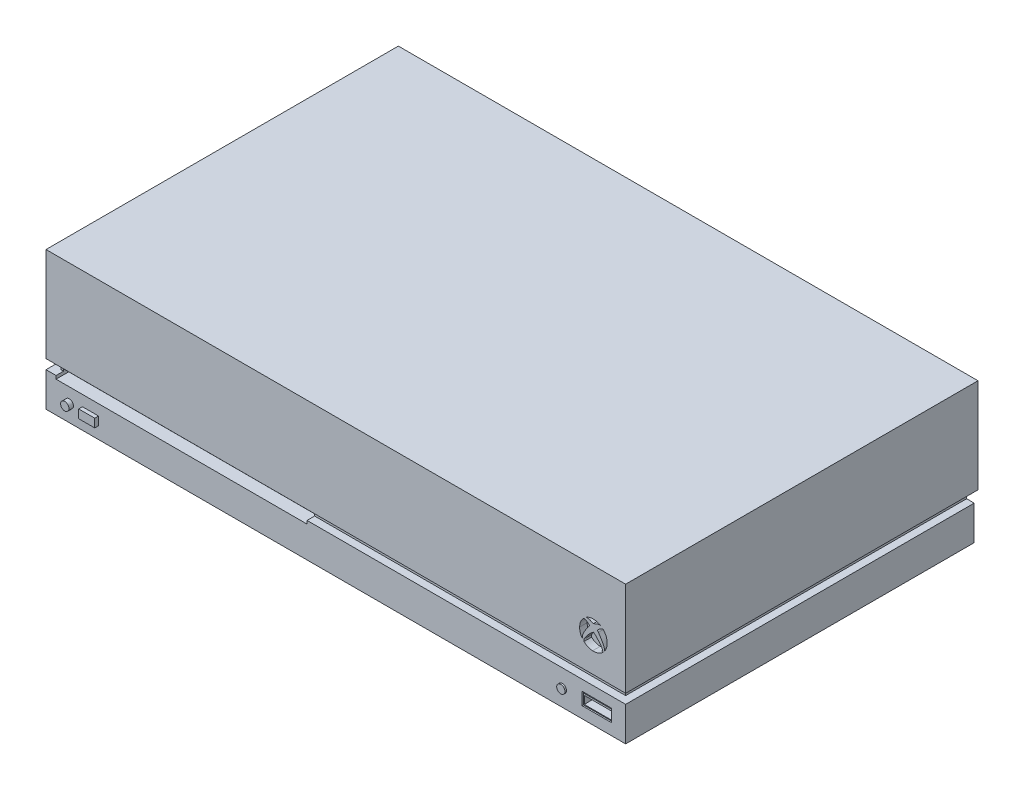
SolidWorks part; units mm, degrees
ref_plane "Front Plane" through (0, 0, 0) normal (0, 0, 1) x (1, 0, 0)
ref_plane "Top Plane" through (0, 0, 0) normal (0, 1, 0) x (1, 0, 0)
ref_plane "Right Plane" through (0, 0, 0) normal (1, 0, 0) x (0, 0, -1)
sketch "Sketch1" plane through (0, 0, 0) normal (0, 1, 0) x (1, 0, 0)
  line L0 (-74.7377, 40.0336) -> (-74.7377, -77.0687)
  line L1 (-74.7377, -77.0687) -> (137.3702, -77.0687)
  line L2 (137.3702, -77.0687) -> (137.3702, 40.0336)
  line L3 (137.3702, 40.0336) -> (-74.7377, 40.0336)
extrude "Boss-Extrude1" add sketch "Sketch1" along normal blind 31.75
sketch "Sketch2" plane through (0, 0, 0) normal (0, -1, 0) x (1, 0, 0)
  line L0 (137.3702, 77.0687) -> (137.3702, -40.0336)
  line L1 (137.3702, -40.0336) -> (-57.3628, -40.0336)
  line L2 (137.3702, -40.0336) -> (-74.7377, -40.0336) construction
  line L3 (-57.3628, -40.0336) -> (-57.3628, 77.0687)
  line L4 (-74.7377, 77.0687) -> (137.3702, 77.0687) construction
  line L5 (-57.3628, 77.0687) -> (137.3702, 77.0687)
extrude "Boss-Extrude2" add sketch "Sketch2" along normal blind 14.732
sketch "Sketch3" plane through (0, 0, 77.0687) normal (0, 0, 1) x (1, 0, 0)
  line L0 (-57.3628, 0) -> (137.3702, 0)
  line L1 (137.3702, 31.75) -> (137.3702, -14.732) construction
  line L2 (137.3702, 0) -> (137.3702, -3.2162)
  line L3 (137.3702, -3.2162) -> (-57.3628, -3.2162)
  line L4 (-57.3628, -14.732) -> (-57.3628, 0) construction
  line L5 (-57.3628, -3.2162) -> (-57.3628, 0)
extrude "Cut-Extrude1" cut sketch "Sketch3" against normal blind 2.54
sketch "Sketch4" plane through (137.3702, 0, 0) normal (1, 0, 0) x (0, 0, -1)
  line L0 (-77.0687, 0) -> (-77.0687, -3.2162)
  line L1 (-77.0687, -3.2162) -> (40.0336, -3.2162)
  line L2 (40.0336, 31.75) -> (40.0336, -14.732) construction
  line L3 (40.0336, -3.2162) -> (40.0336, 0)
  line L4 (40.0336, 0) -> (-77.0687, 0)
extrude "Cut-Extrude2" cut sketch "Sketch4" against normal blind 2.54
sketch "Sketch5" plane through (0, 0, -40.0336) normal (0, 0, -1) x (-1, 0, 0)
  line L0 (-137.3702, 0) -> (-137.3702, -3.2162)
  line L1 (-137.3702, -3.2162) -> (57.3628, -3.2162)
  line L2 (57.3628, -14.732) -> (57.3628, 0) construction
  line L3 (57.3628, -3.2162) -> (57.3628, 0)
  line L4 (57.3628, 0) -> (-137.3702, 0)
extrude "Cut-Extrude4" cut sketch "Sketch5" against normal blind 2.54
sketch "Sketch6" plane through (-57.3628, 0, 0) normal (-1, 0, 0) x (0, 0, 1)
  line L0 (-37.4936, 0) -> (-37.4936, -3.2162)
  line L1 (-37.4936, -3.2162) -> (74.5287, -3.2162)
  line L2 (74.5287, 0) -> (-37.4936, 0)
  line L3 (74.5287, 0) -> (74.5287, -3.2162)
extrude "Cut-Extrude6" cut sketch "Sketch6" against normal blind 2.54
sketch "Sketch7" plane through (0, 0, 77.0687) normal (0, 0, 1) x (1, 0, 0)
  line L0 (137.3702, -3.2162) -> (137.3702, -14.732) construction
  line L1 (122.7433, -10.922) -> (132.5442, -10.922)
  line L2 (122.7433, -10.922) -> (122.7433, -6.7111)
  line L3 (122.7433, -6.7111) -> (132.5442, -6.7111)
  line L4 (132.5442, -10.922) -> (132.5442, -6.7111)
  line L5 (137.3702, -14.732) -> (-57.3628, -14.732) construction
  dimension "D1" = 3.81
  dimension "D2" = 4.826
extrude "Cut-Extrude8" cut sketch "Sketch7" against normal blind 5.08
sketch "Sketch8" plane through (0, 0, 71.9887) normal (0, 0, 1) x (1, 0, 0)
  line L0 (132.5442, -6.7111) -> (122.7433, -6.7111)
  line L1 (122.7433, -6.7111) -> (122.7433, -10.922)
  line L2 (122.7433, -10.922) -> (132.5442, -10.922)
  line L3 (122.7433, -10.922) -> (132.5442, -10.922) construction
  line L4 (132.5442, -10.922) -> (132.5442, -6.7111) construction
  line L5 (132.5442, -10.922) -> (132.5442, -6.7111)
extrude "Boss-Extrude3" add sketch "Sketch8" along normal blind 4.6314
sketch "Sketch9" plane through (0, 0, 76.6201) normal (0, 0, 1) x (1, 0, 0)
  line L0 (132.4085, -7.994) -> (123.0238, -7.994)
  line L1 (123.0238, -7.994) -> (123.0238, -10.6263)
  line L2 (123.0238, -10.6263) -> (132.4085, -10.6263)
  line L3 (132.4085, -10.6263) -> (132.4085, -7.994)
extrude "Cut-Extrude9" cut sketch "Sketch9" against normal blind 4.6314
sketch "Sketch10" plane through (0, 0, 76.6201) normal (0, 0, 1) x (1, 0, 0)
  line L0 (132.5442, -7.4299) -> (122.7433, -7.4299)
  line L1 (132.5442, -10.922) -> (132.5442, -6.7111) construction
  line L2 (122.7433, -6.7111) -> (122.7433, -10.922) construction
  line L3 (122.7433, -7.4299) -> (122.7433, -6.7111)
  line L4 (132.5442, -6.7111) -> (122.7433, -6.7111) construction
  line L5 (122.7433, -6.7111) -> (132.5442, -6.7111)
  line L6 (132.5442, -6.7111) -> (132.5442, -7.4299)
extrude "Cut-Extrude10" cut sketch "Sketch10" against normal blind 4.6314
sketch "Sketch11" plane through (0, 0, 77.0687) normal (0, 0, 1) x (1, 0, 0)
  circle A0 centre (116.1002, -9.1661) radius 1.397
  dimension "D1" = 2.794
extrude "Boss-Extrude4" add sketch "Sketch11" along normal blind 0.508
sketch "Sketch13" plane through (0, 0, 77.0687) normal (0, 0, 1) x (1, 0, 0)
  circle A0 centre (-49.5395, -9.1661) radius 1.397
  dimension "D1" = 2.794
extrude "Boss-Extrude5" add sketch "Sketch13" along normal blind 1.524
sketch "Sketch14" plane through (0, 0, 77.0687) normal (0, 0, 1) x (1, 0, 0)
  line L0 (-53.9904, -3.2162) -> (-53.9904, -4.2897)
  line L1 (-57.3628, -3.2162) -> (137.3702, -3.2162) construction
  line L2 (-53.9904, -4.2897) -> (30.3322, -4.2897)
  line L3 (30.3322, -4.2897) -> (30.3322, -3.2162)
  line L4 (30.3322, -3.2162) -> (-53.9904, -3.2162)
extrude "Cut-Extrude12" cut sketch "Sketch14" against normal blind 12.7
sketch "Sketch15" plane through (0, 0, 74.5287) normal (0, 0, 1) x (1, 0, 0)
  line L0 (-53.9904, -3.2162) -> (-53.9904, -2.9114)
  line L1 (-53.9904, -2.9114) -> (30.3322, -2.9114)
  line L2 (30.3322, -2.9114) -> (30.3322, -3.2162)
  line L3 (30.3322, -3.2162) -> (-53.9904, -3.2162)
  dimension "D1" = 0.3048
extrude "Cut-Extrude14" cut sketch "Sketch15" against normal blind 10.16
sketch "Sketch17" plane through (0, 0, 77.0687) normal (0, 0, 1) x (1, 0, 0)
  line L0 (-39.7277, -7.8666) -> (-45.1141, -7.8666)
  line L1 (-45.1141, -7.8666) -> (-45.1141, -10.7177)
  line L2 (-45.1141, -10.7177) -> (-39.7277, -10.7177)
  line L3 (-39.7277, -10.7177) -> (-39.7277, -7.8666)
extrude "Boss-Extrude7" add sketch "Sketch17" along normal blind 1.27
sketch "Sketch19" plane through (0, 0, 77.0687) normal (0, 0, 1) x (1, 0, 0)
  line L0 (-65.632, 31.75) -> (-65.632, 0)
  line L1 (-74.7377, 31.75) -> (137.3702, 31.75) construction
  line L2 (-74.7377, 0) -> (137.3702, 0) construction
  line L3 (-65.632, 0) -> (-74.7377, 0)
  line L4 (-74.7377, 0) -> (-74.7377, 31.75)
  line L5 (-74.7377, 31.75) -> (-65.632, 31.75)
extrude "Cut-Extrude17" cut sketch "Sketch19" against normal blind 133.35
sketch "Sketch20" plane through (0, 0, 74.5287) normal (0, 0, 1) x (1, 0, 0)
  line L0 (30.3322, -2.9114) -> (30.3322, -2.5679)
  line L1 (30.3322, -2.5679) -> (-53.9904, -2.5679)
  line L2 (-53.9904, -2.5679) -> (-53.9904, -2.9114)
  line L3 (-53.9904, -2.9114) -> (30.3322, -2.9114)
extrude "Cut-Extrude20" cut sketch "Sketch20" against normal blind 10.16
sketch "Sketch21" plane through (0, 0, -37.4936) normal (0, 0, -1) x (-1, 0, 0)
  line L0 (-134.8302, 0) -> (-134.8302, -3.2162)
  line L1 (-134.8302, -3.2162) -> (54.8228, -3.2162)
  line L2 (54.8228, -3.2162) -> (54.8228, 0)
  line L3 (54.8228, 0) -> (-134.8302, 0)
extrude "Boss-Extrude8" add sketch "Sketch21" along normal blind 2.54
sketch "Sketch24" plane through (0, 0, -40.0336) normal (0, 0, -1) x (-1, 0, 0)
  line L0 (-135.3382, 29.718) -> (63.6, 29.718)
  line L1 (63.6, 29.718) -> (63.6, 0)
  line L2 (-135.3382, 29.718) -> (-135.3382, 0)
  line L3 (-137.3702, 0) -> (-134.8302, 0) construction
  line L5 (54.8228, 0) -> (65.632, 0) construction
  line L6 (-137.3702, 31.75) -> (-137.3702, 0) construction
  line L7 (65.632, 0) -> (65.632, 31.75) construction
  line L8 (-137.3702, 31.75) -> (65.632, 31.75) construction
  line L21 (57.3628, -14.732) -> (57.3628, -3.2162)
  line L22 (57.3628, -3.2162) -> (54.8228, -3.2162)
  line L23 (54.8228, -3.2162) -> (54.8228, 0)
  line L24 (54.8228, 0) -> (65.632, 0)
  line L25 (65.632, 0) -> (65.632, 31.75)
  line L26 (65.632, 31.75) -> (-137.3702, 31.75)
  line L27 (-137.3702, 31.75) -> (-137.3702, 0)
  line L28 (-137.3702, 0) -> (-134.8302, 0)
  line L29 (-134.8302, 0) -> (-134.8302, -3.2162)
  line L30 (-134.8302, -3.2162) -> (-137.3702, -3.2162)
  line L31 (-137.3702, -3.2162) -> (-137.3702, -14.732)
  line L32 (-137.3702, -14.732) -> (57.3628, -14.732)
  line L36 (63.6, 0) -> (65.632, 0)
  line L37 (65.632, 0) -> (65.632, 31.75)
  line L38 (65.632, 31.75) -> (-137.3702, 31.75)
  line L39 (-137.3702, 31.75) -> (-137.3702, 0)
  line L40 (-137.3702, 0) -> (-135.3382, 0)
  dimension "D1" = 2.032
  dimension "D2" = 2.032
  dimension "D3" = 2.032
  dimension "D4" = 0
extrude "Boss-Extrude9" add sketch "Sketch24" along normal blind 1.27 contours L36 L37 L38 L39 L40 L2 L0 L1
sketch "Sketch25" plane through (0, 0, -40.0336) normal (0, 0, -1) x (-1, 0, 0)
  circle A0 centre (-131.916, 26.6592) radius 0.9515
  circle A1 centre (-129.376, 26.6592) radius 0.9515
  circle A2 centre (-126.836, 26.6592) radius 0.9515
  circle A3 centre (-124.296, 26.6592) radius 0.9515
  circle A4 centre (-121.756, 26.6592) radius 0.9515
  circle A5 centre (-119.216, 26.6592) radius 0.9515
  circle A6 centre (-116.676, 26.6592) radius 0.9515
  circle A7 centre (-114.136, 26.6592) radius 0.9515
  circle A8 centre (-111.596, 26.6592) radius 0.9515
  circle A9 centre (-109.056, 26.6592) radius 0.9515
  circle A10 centre (-106.516, 26.6592) radius 0.9515
  circle A11 centre (-103.976, 26.6592) radius 0.9515
  circle A12 centre (-101.436, 26.6592) radius 0.9515
  circle A13 centre (-98.896, 26.6592) radius 0.9515
  circle A14 centre (-96.356, 26.6592) radius 0.9515
  circle A15 centre (-93.816, 26.6592) radius 0.9515
  circle A16 centre (-91.276, 26.6592) radius 0.9515
  circle A17 centre (-88.736, 26.6592) radius 0.9515
  circle A18 centre (-86.196, 26.6592) radius 0.9515
  circle A19 centre (-83.656, 26.6592) radius 0.9515
  circle A20 centre (-81.116, 26.6592) radius 0.9515
  circle A21 centre (-78.576, 26.6592) radius 0.9515
  circle A22 centre (-76.036, 26.6592) radius 0.9515
  circle A23 centre (-73.496, 26.6592) radius 0.9515
  circle A24 centre (-70.956, 26.6592) radius 0.9515
  circle A25 centre (-68.416, 26.6592) radius 0.9515
  circle A26 centre (-65.876, 26.6592) radius 0.9515
  circle A27 centre (-63.336, 26.6592) radius 0.9515
  circle A28 centre (-60.796, 26.6592) radius 0.9515
  circle A29 centre (-58.256, 26.6592) radius 0.9515
  circle A30 centre (-55.716, 26.6592) radius 0.9515
  circle A31 centre (-53.176, 26.6592) radius 0.9515
  circle A32 centre (-50.636, 26.6592) radius 0.9515
  circle A33 centre (-48.096, 26.6592) radius 0.9515
  circle A34 centre (-45.556, 26.6592) radius 0.9515
  circle A35 centre (-43.016, 26.6592) radius 0.9515
  circle A36 centre (-40.476, 26.6592) radius 0.9515
  circle A37 centre (-37.936, 26.6592) radius 0.9515
  circle A38 centre (-35.396, 26.6592) radius 0.9515
  circle A39 centre (-32.856, 26.6592) radius 0.9515
  circle A40 centre (-30.316, 26.6592) radius 0.9515
  circle A41 centre (-27.776, 26.6592) radius 0.9515
  circle A42 centre (-25.236, 26.6592) radius 0.9515
  circle A43 centre (-22.696, 26.6592) radius 0.9515
  circle A44 centre (-20.156, 26.6592) radius 0.9515
  circle A45 centre (-17.616, 26.6592) radius 0.9515
  circle A46 centre (-15.076, 26.6592) radius 0.9515
  circle A47 centre (-12.536, 26.6592) radius 0.9515
  circle A48 centre (-9.996, 26.6592) radius 0.9515
  circle A49 centre (-7.456, 26.6592) radius 0.9515
  circle A50 centre (-4.916, 26.6592) radius 0.9515
  circle A51 centre (-2.376, 26.6592) radius 0.9515
  circle A52 centre (0.164, 26.6592) radius 0.9515
  circle A53 centre (2.704, 26.6592) radius 0.9515
  circle A54 centre (5.244, 26.6592) radius 0.9515
  circle A55 centre (7.784, 26.6592) radius 0.9515
  circle A56 centre (10.324, 26.6592) radius 0.9515
  circle A57 centre (12.864, 26.6592) radius 0.9515
  circle A58 centre (15.404, 26.6592) radius 0.9515
  circle A59 centre (17.944, 26.6592) radius 0.9515
  circle A60 centre (20.484, 26.6592) radius 0.9515
  circle A61 centre (23.024, 26.6592) radius 0.9515
  circle A62 centre (25.564, 26.6592) radius 0.9515
  circle A63 centre (-131.916, 24.1192) radius 0.889
  circle A64 centre (-129.376, 24.1192) radius 0.889
  circle A65 centre (-126.836, 24.1192) radius 0.889
  circle A66 centre (-124.296, 24.1192) radius 0.889
  circle A67 centre (-121.756, 24.1192) radius 0.889
  circle A68 centre (-119.216, 24.1192) radius 0.889
  circle A69 centre (-116.676, 24.1192) radius 0.889
  circle A70 centre (-114.136, 24.1192) radius 0.889
  circle A71 centre (-111.596, 24.1192) radius 0.889
  circle A72 centre (-109.056, 24.1192) radius 0.889
  circle A73 centre (-106.516, 24.1192) radius 0.889
  circle A74 centre (-103.976, 24.1192) radius 0.889
  circle A75 centre (-101.436, 24.1192) radius 0.889
  circle A76 centre (-98.896, 24.1192) radius 0.889
  circle A77 centre (-96.356, 24.1192) radius 0.889
  circle A78 centre (-93.816, 24.1192) radius 0.889
  circle A79 centre (-91.276, 24.1192) radius 0.889
  circle A80 centre (-88.736, 24.1192) radius 0.889
  circle A81 centre (-86.196, 24.1192) radius 0.889
  circle A82 centre (-83.656, 24.1192) radius 0.889
  circle A83 centre (-81.116, 24.1192) radius 0.889
  circle A84 centre (-78.576, 24.1192) radius 0.889
  circle A85 centre (-76.036, 24.1192) radius 0.889
  circle A86 centre (-73.496, 24.1192) radius 0.889
  circle A87 centre (-70.956, 24.1192) radius 0.889
  circle A88 centre (-68.416, 24.1192) radius 0.889
  circle A89 centre (-65.876, 24.1192) radius 0.889
  circle A90 centre (-63.336, 24.1192) radius 0.889
  circle A91 centre (-60.796, 24.1192) radius 0.889
  circle A92 centre (-58.256, 24.1192) radius 0.889
  circle A93 centre (-55.716, 24.1192) radius 0.889
  circle A94 centre (-53.176, 24.1192) radius 0.889
  circle A95 centre (-50.636, 24.1192) radius 0.889
  circle A96 centre (-48.096, 24.1192) radius 0.889
  circle A97 centre (-45.556, 24.1192) radius 0.889
  circle A98 centre (-43.016, 24.1192) radius 0.889
  circle A99 centre (-40.476, 24.1192) radius 0.889
  circle A100 centre (-37.936, 24.1192) radius 0.889
  circle A101 centre (-35.396, 24.1192) radius 0.889
  circle A102 centre (-32.856, 24.1192) radius 0.889
  circle A103 centre (-30.316, 24.1192) radius 0.889
  circle A104 centre (-27.776, 24.1192) radius 0.889
  circle A105 centre (-25.236, 24.1192) radius 0.889
  circle A106 centre (-22.696, 24.1192) radius 0.889
  circle A107 centre (-20.156, 24.1192) radius 0.889
  circle A108 centre (-17.616, 24.1192) radius 0.889
  circle A109 centre (-15.076, 24.1192) radius 0.889
  circle A110 centre (-12.536, 24.1192) radius 0.889
  circle A111 centre (-9.996, 24.1192) radius 0.889
  circle A112 centre (-7.456, 24.1192) radius 0.889
  circle A113 centre (-4.916, 24.1192) radius 0.889
  circle A114 centre (-2.376, 24.1192) radius 0.889
  circle A115 centre (0.164, 24.1192) radius 0.889
  circle A116 centre (2.704, 24.1192) radius 0.889
  circle A117 centre (5.244, 24.1192) radius 0.889
  circle A118 centre (7.784, 24.1192) radius 0.889
  circle A119 centre (10.324, 24.1192) radius 0.889
  circle A120 centre (12.864, 24.1192) radius 0.889
  circle A121 centre (15.404, 24.1192) radius 0.889
  circle A122 centre (17.944, 24.1192) radius 0.889
  circle A123 centre (20.484, 24.1192) radius 0.889
  circle A124 centre (23.024, 24.1192) radius 0.889
  circle A125 centre (25.564, 24.1192) radius 0.889
  circle A126 centre (-131.916, 21.5792) radius 0.889
  circle A127 centre (-129.376, 21.5792) radius 0.889
  circle A128 centre (-126.836, 21.5792) radius 0.889
  circle A129 centre (-124.296, 21.5792) radius 0.889
  circle A130 centre (-121.756, 21.5792) radius 0.889
  circle A131 centre (-119.216, 21.5792) radius 0.889
  circle A132 centre (-116.676, 21.5792) radius 0.889
  circle A133 centre (-114.136, 21.5792) radius 0.889
  circle A134 centre (-111.596, 21.5792) radius 0.889
  circle A135 centre (-109.056, 21.5792) radius 0.889
  circle A136 centre (-106.516, 21.5792) radius 0.889
  circle A137 centre (-103.976, 21.5792) radius 0.889
  circle A138 centre (-101.436, 21.5792) radius 0.889
  circle A139 centre (-98.896, 21.5792) radius 0.889
  circle A140 centre (-96.356, 21.5792) radius 0.889
  circle A141 centre (-93.816, 21.5792) radius 0.889
  circle A142 centre (-91.276, 21.5792) radius 0.889
  circle A143 centre (-88.736, 21.5792) radius 0.889
  circle A144 centre (-86.196, 21.5792) radius 0.889
  circle A145 centre (-83.656, 21.5792) radius 0.889
  circle A146 centre (-81.116, 21.5792) radius 0.889
  circle A147 centre (-78.576, 21.5792) radius 0.889
  circle A148 centre (-76.036, 21.5792) radius 0.889
  circle A149 centre (-73.496, 21.5792) radius 0.889
  circle A150 centre (-70.956, 21.5792) radius 0.889
  circle A151 centre (-68.416, 21.5792) radius 0.889
  circle A152 centre (-65.876, 21.5792) radius 0.889
  circle A153 centre (-63.336, 21.5792) radius 0.889
  circle A154 centre (-60.796, 21.5792) radius 0.889
  circle A155 centre (-58.256, 21.5792) radius 0.889
  circle A156 centre (-55.716, 21.5792) radius 0.889
  circle A157 centre (-53.176, 21.5792) radius 0.889
  circle A158 centre (-50.636, 21.5792) radius 0.889
  circle A159 centre (-48.096, 21.5792) radius 0.889
  circle A160 centre (-45.556, 21.5792) radius 0.889
  circle A161 centre (-43.016, 21.5792) radius 0.889
  circle A162 centre (-40.476, 21.5792) radius 0.889
  circle A163 centre (-37.936, 21.5792) radius 0.889
  circle A164 centre (-35.396, 21.5792) radius 0.889
  circle A165 centre (-32.856, 21.5792) radius 0.889
  circle A166 centre (-30.316, 21.5792) radius 0.889
  circle A167 centre (-27.776, 21.5792) radius 0.889
  circle A168 centre (-25.236, 21.5792) radius 0.889
  circle A169 centre (-22.696, 21.5792) radius 0.889
  circle A170 centre (-20.156, 21.5792) radius 0.889
  circle A171 centre (-17.616, 21.5792) radius 0.889
  circle A172 centre (-15.076, 21.5792) radius 0.889
  circle A173 centre (-12.536, 21.5792) radius 0.889
  circle A174 centre (-9.996, 21.5792) radius 0.889
  circle A175 centre (-7.456, 21.5792) radius 0.889
  circle A176 centre (-4.916, 21.5792) radius 0.889
  circle A177 centre (-2.376, 21.5792) radius 0.889
  circle A178 centre (0.164, 21.5792) radius 0.889
  circle A179 centre (2.704, 21.5792) radius 0.889
  circle A180 centre (5.244, 21.5792) radius 0.889
  circle A181 centre (7.784, 21.5792) radius 0.889
  circle A182 centre (10.324, 21.5792) radius 0.889
  circle A183 centre (12.864, 21.5792) radius 0.889
  circle A184 centre (15.404, 21.5792) radius 0.889
  circle A185 centre (17.944, 21.5792) radius 0.889
  circle A186 centre (20.484, 21.5792) radius 0.889
  circle A187 centre (23.024, 21.5792) radius 0.889
  circle A188 centre (25.564, 21.5792) radius 0.889
  circle A189 centre (-131.916, 19.0392) radius 0.889
  circle A190 centre (-129.376, 19.0392) radius 0.889
  circle A191 centre (-126.836, 19.0392) radius 0.889
  circle A192 centre (-124.296, 19.0392) radius 0.889
  circle A193 centre (-121.756, 19.0392) radius 0.889
  circle A194 centre (-119.216, 19.0392) radius 0.889
  circle A195 centre (-116.676, 19.0392) radius 0.889
  circle A196 centre (-114.136, 19.0392) radius 0.889
  circle A197 centre (-111.596, 19.0392) radius 0.889
  circle A198 centre (-109.056, 19.0392) radius 0.889
  circle A199 centre (-106.516, 19.0392) radius 0.889
  circle A200 centre (-103.976, 19.0392) radius 0.889
  circle A201 centre (-101.436, 19.0392) radius 0.889
  circle A202 centre (-98.896, 19.0392) radius 0.889
  circle A203 centre (-96.356, 19.0392) radius 0.889
  circle A204 centre (-93.816, 19.0392) radius 0.889
  circle A205 centre (-91.276, 19.0392) radius 0.889
  circle A206 centre (-88.736, 19.0392) radius 0.889
  circle A207 centre (-86.196, 19.0392) radius 0.889
  circle A208 centre (-83.656, 19.0392) radius 0.889
  circle A209 centre (-81.116, 19.0392) radius 0.889
  circle A210 centre (-78.576, 19.0392) radius 0.889
  circle A211 centre (-76.036, 19.0392) radius 0.889
  circle A212 centre (-73.496, 19.0392) radius 0.889
  circle A213 centre (-70.956, 19.0392) radius 0.889
  circle A214 centre (-68.416, 19.0392) radius 0.889
  circle A215 centre (-65.876, 19.0392) radius 0.889
  circle A216 centre (-63.336, 19.0392) radius 0.889
  circle A217 centre (-60.796, 19.0392) radius 0.889
  circle A218 centre (-58.256, 19.0392) radius 0.889
  circle A219 centre (-55.716, 19.0392) radius 0.889
  circle A220 centre (-53.176, 19.0392) radius 0.889
  circle A221 centre (-50.636, 19.0392) radius 0.889
  circle A222 centre (-48.096, 19.0392) radius 0.889
  circle A223 centre (-45.556, 19.0392) radius 0.889
  circle A224 centre (-43.016, 19.0392) radius 0.889
  circle A225 centre (-40.476, 19.0392) radius 0.889
  circle A226 centre (-37.936, 19.0392) radius 0.889
  circle A227 centre (-35.396, 19.0392) radius 0.889
  circle A228 centre (-32.856, 19.0392) radius 0.889
  circle A229 centre (-30.316, 19.0392) radius 0.889
  circle A230 centre (-27.776, 19.0392) radius 0.889
  circle A231 centre (-25.236, 19.0392) radius 0.889
  circle A232 centre (-22.696, 19.0392) radius 0.889
  circle A233 centre (-20.156, 19.0392) radius 0.889
  circle A234 centre (-17.616, 19.0392) radius 0.889
  circle A235 centre (-15.076, 19.0392) radius 0.889
  circle A236 centre (-12.536, 19.0392) radius 0.889
  circle A237 centre (-9.996, 19.0392) radius 0.889
  circle A238 centre (-7.456, 19.0392) radius 0.889
  circle A239 centre (-4.916, 19.0392) radius 0.889
  circle A240 centre (-2.376, 19.0392) radius 0.889
  circle A241 centre (0.164, 19.0392) radius 0.889
  circle A242 centre (2.704, 19.0392) radius 0.889
  circle A243 centre (5.244, 19.0392) radius 0.889
  circle A244 centre (7.784, 19.0392) radius 0.889
  circle A245 centre (10.324, 19.0392) radius 0.889
  circle A246 centre (12.864, 19.0392) radius 0.889
  circle A247 centre (15.404, 19.0392) radius 0.889
  circle A248 centre (17.944, 19.0392) radius 0.889
  circle A249 centre (20.484, 19.0392) radius 0.889
  circle A250 centre (23.024, 19.0392) radius 0.889
  circle A251 centre (25.564, 19.0392) radius 0.889
  dimension "D2" = 2.54
  dimension "D3" = 1.778
  dimension "D4" = 1.9029
  dimension "D6" = 2.54
  dimension "D7" = 1.778
  dimension "D9" = 2.54
  dimension "D10" = 1.778
  dimension "D1" = 63
  dimension "D5" = 63
  dimension "D8" = 63
  dimension "D11" = 63
extrude "Cut-Extrude23" cut sketch "Sketch25" against normal blind 13.97
sketch "Sketch26" plane through (0, 0, -40.0336) normal (0, 0, -1) x (-1, 0, 0)
  line L8 (28.9927, 29.718) -> (28.9927, 0)
  line L9 (-135.3382, 29.718) -> (63.6, 29.718) construction
  line L10 (28.9927, 0) -> (54.8228, 0)
  line L11 (54.8228, 0) -> (54.8228, -0.4442)
  line L12 (54.8228, -3.2162) -> (54.8228, 0) construction
  line L13 (54.8228, -0.4442) -> (28.4648, -0.4442)
  line L14 (28.4648, -0.4442) -> (28.4648, 29.718)
  line L15 (28.4648, 29.718) -> (28.9927, 29.718)
extrude "Cut-Extrude28" cut sketch "Sketch26" against normal blind 13.97 contours L15 L8 L10 L11 L13 L14
sketch "Sketch27" plane through (0, 0, -40.0336) normal (0, 0, -1) x (-1, 0, 0)
  line L5 (43.5719, 14.4052) -> (50.9349, 14.4052)
  line L6 (43.5719, 14.4052) -> (43.5719, 10.9849)
  line L7 (43.5719, 10.9849) -> (50.9349, 10.9849)
  line L8 (50.9349, 14.4052) -> (50.9349, 10.9849)
extrude "Cut-Extrude29" cut sketch "Sketch27" against normal blind 13.97
sketch "Sketch28" plane through (0, 0, -40.0336) normal (0, 0, -1) x (-1, 0, 0)
  line L0 (-126.6517, 5.0454) -> (-120.35, 5.0454) construction
  line L1 (-126.6517, 8.3464) -> (-120.35, 8.3464)
  line L2 (-126.6517, 1.7445) -> (-120.35, 1.7445)
  line L3 (-1000.1763, -459.4468) -> (-111.5096, -459.4468) construction
  line L4 (-83.9499, 4.5855) -> (-86.7908, 1.7445)
  line L5 (-86.7908, 1.7445) -> (-94.3599, 1.7445)
  line L6 (-94.3599, 1.7445) -> (-96.4957, 3.8803)
  line L7 (-96.4957, 3.8803) -> (-96.4957, 7.8543)
  line L8 (-96.4957, 7.8543) -> (-83.9499, 7.8543)
  line L9 (-83.9499, 7.8543) -> (-83.9499, 4.5855)
  line L10 (-65.3081, 7.8543) -> (-65.3081, 4.5855)
  line L11 (-65.3081, 4.5855) -> (-68.149, 1.7445)
  line L12 (-68.149, 1.7445) -> (-75.7181, 1.7445)
  line L13 (-75.7181, 1.7445) -> (-77.8539, 3.8803)
  line L14 (-77.8539, 3.8803) -> (-77.8539, 7.8543)
  line L15 (-77.8539, 7.8543) -> (-65.3081, 7.8543)
  line L16 (-40.9735, 1.7445) -> (-40.9735, 7.8543)
  line L17 (-59.2121, 1.7445) -> (-47.0695, 1.7445)
  line L18 (-59.2121, 1.7445) -> (-59.2121, 7.8543)
  line L19 (-59.2121, 7.8543) -> (-47.0695, 7.8543)
  line L20 (-47.0695, 1.7445) -> (-47.0695, 7.8543)
  line L21 (-40.9735, 1.7445) -> (-28.831, 1.7445)
  line L22 (-28.831, 1.7445) -> (-28.831, 7.8543)
  line L23 (-40.9735, 7.8543) -> (-28.831, 7.8543)
  line L24 (-5.3824, 10.5267) -> (2.9257, 10.5267)
  line L25 (2.9257, 10.5267) -> (2.9257, 0)
  line L26 (2.9257, 0) -> (-5.3824, 0)
  line L27 (-5.3824, 0) -> (-5.3824, 10.5267)
  line L28 (25.0805, 10.5267) -> (15.0682, 10.5267)
  line L29 (15.0682, 10.5267) -> (15.0682, 0)
  line L30 (15.0682, 0) -> (25.0805, 0)
  line L31 (25.0805, 0) -> (25.0805, 10.5267)
  arc A0 (-126.6517, 8.3464) -> (-126.6517, 1.7445) centre (-126.6517, 5.0454) ccw
  arc A1 (-120.35, 1.7445) -> (-120.35, 8.3464) centre (-120.35, 5.0454) ccw
  circle A2 centre (-18.59, 4.5855) radius 2.5563
  circle A3 centre (-18.59, 4.5855) radius 3.8988
  point P2 (-123.5009, 5.0454)
  dimension "D3" = 6.096
  dimension "D4" = 6.096
  dimension "D5" = 6.096
  dimension "D1" = 2
  dimension "D2" = 2
extrude "Cut-Extrude30" cut sketch "Sketch28" against normal blind 7.62
sketch "Sketch29" plane through (0, 0, -40.0336) normal (0, 0, -1) x (-1, 0, 0)
  line L0 (-77.216, 14.2428) -> (-65.4628, 14.2428)
  text T0 "H D M I OUT " font "Century Gothic" height in points 3
sketch "Sketch30" plane through (0, 0, -40.0336) normal (0, 0, -1) x (-1, 0, 0)
  line L0 (-126.6517, 5.0454) -> (-120.35, 5.0454) construction
  line L1 (-126.6517, 6.9588) -> (-120.35, 6.9588)
  line L2 (-126.6517, 3.1321) -> (-120.35, 3.1321)
  arc A1 (-126.6517, 6.9588) -> (-126.6517, 3.1321) centre (-126.6517, 5.0454) ccw
  arc A2 (-120.35, 3.1321) -> (-120.35, 6.9588) centre (-120.35, 5.0454) ccw
  circle A3 centre (-126.6517, 5.0454) radius 1.0146
  circle A4 centre (-120.35, 5.0454) radius 1.1066
  text T0 "H D M I IN" font "Century Gothic" height in points 3
  point P3 (-123.5009, 5.0454)
extrude "Boss-Extrude10" add sketch "Sketch30" against normal blind 3.81
sketch "Sketch31" plane through (0, 0, 77.0687) normal (0, 0, 1) x (1, 0, 0)
  line L0 (292.423, 518.7459) -> (975.0897, 518.7459) construction
  spline S0 degree 3 poles (129.7417, 14.8584) (131.4157, 13.366) (131.6532, 10.436) (130.2544, 8.6882) knots 0 0 0 0 1 1 1 1
  spline S1 degree 2 poles (130.2544, 8.6882) (130.3, 9.0131) (130.2516, 9.3398) knots 0 0 0 1 1 1
  spline S2 degree 3 poles (130.2516, 9.3398) (129.9699, 10.7688) (128.9396, 11.9522) (128.2074, 13.1567) knots 0 0 0 0 1 1 1 1
  spline S3 degree 1 poles (128.2074, 13.1567) (127.8348, 13.6165) knots 0 0 1 1
  spline S4 degree 2 poles (127.8348, 13.6165) (128.6091, 14.519) (129.7417, 14.8584) knots 0 0 0 1 1 1
  spline S5 degree 2 poles (125.2329, 13.6165) (124.4822, 14.517) (123.3866, 14.8584) knots 0 0 0 1 1 1
  spline S6 degree 2 poles (123.3866, 14.8584) (121.9404, 13.5584) (121.919, 11.5687) knots 0 0 0 1 1 1
  spline S7 degree 2 poles (121.919, 11.5687) (121.8716, 9.9466) (122.8247, 8.6882) knots 0 0 0 1 1 1
  spline S8 degree 2 poles (122.8247, 8.6882) (122.7284, 9.2193) (122.918, 9.7431) knots 0 0 0 1 1 1
  spline S9 degree 2 poles (122.918, 9.7431) (123.2132, 10.613) (123.7099, 11.3934) knots 0 0 0 1 1 1
  spline S10 degree 2 poles (123.7099, 11.3934) (124.3661, 12.5788) (125.2329, 13.6165) knots 0 0 0 1 1 1
  spline S11 degree 2 poles (126.5213, 14.8394) (127.105, 15.1228) (127.713, 15.3506) knots 0 0 0 1 1 1
  spline S12 degree 2 poles (127.713, 15.3506) (128.3063, 15.59) (128.9431, 15.5026) knots 0 0 0 1 1 1
  spline S13 degree 2 poles (128.9431, 15.5026) (128.374, 15.851) (127.7293, 16.0154) knots 0 0 0 1 1 1
  spline S14 degree 2 poles (127.7293, 16.0154) (127.3883, 16.1289) (127.0313, 16.1446) knots 0 0 0 1 1 1
  spline S15 degree 2 poles (127.0313, 16.1446) (126.4754, 16.1936) (125.9202, 16.1344) knots 0 0 0 1 1 1
  spline S16 degree 2 poles (125.9202, 16.1344) (125.1935, 16.0523) (124.5356, 15.7314) knots 0 0 0 1 1 1
  spline S17 degree 1 poles (124.5356, 15.7314) (124.2458, 15.5865) knots 0 0 1 1
  spline S18 degree 2 poles (124.2458, 15.5865) (124.205, 15.5638) (124.1874, 15.5192) knots 0 0 0 1 1 1
  spline S19 degree 2 poles (124.1874, 15.5192) (124.5431, 15.5406) (124.8948, 15.4856) knots 0 0 0 1 1 1
  spline S20 degree 2 poles (124.8948, 15.4856) (125.7461, 15.2617) (126.5213, 14.8394) knots 0 0 0 1 1 1
  spline S21 degree 2 poles (126.5213, 12.3959) (126.6077, 12.3851) (126.6735, 12.3242) knots 0 0 0 1 1 1
  spline S22 degree 2 poles (126.6735, 12.3242) (127.9183, 11.2319) (128.9431, 9.9322) knots 0 0 0 1 1 1
  spline S23 degree 2 poles (128.9431, 9.9322) (129.5678, 9.0879) (129.7417, 8.0734) knots 0 0 0 1 1 1
  spline S24 degree 2 poles (129.7417, 8.0734) (128.2737, 6.7811) (126.2654, 6.8259) knots 0 0 0 1 1 1
  spline S25 degree 2 poles (126.2654, 6.8259) (124.6137, 6.9293) (123.3866, 8.0734) knots 0 0 0 1 1 1
  spline S26 degree 2 poles (123.3866, 8.0734) (123.2293, 8.6642) (123.6112, 9.1752) knots 0 0 0 1 1 1
  spline S27 degree 2 poles (123.6112, 9.1752) (124.7664, 11.0557) (126.5213, 12.3959) knots 0 0 0 1 1 1
extrude "Cut-Extrude33" cut sketch "Sketch31" against normal blind 2.54
sketch "Sketch32" plane through (0, 0, 0) normal (0, 0, 1) x (1, 0, 0)
  line L0 (-57.3628, -3.2162) -> (-57.3628, 44.2275)
  line L1 (-57.3628, 44.2275) -> (-72.2158, 44.2275)
  line L2 (-72.2158, 44.2275) -> (-72.2158, -3.2162)
  line L3 (-72.2158, -3.2162) -> (-59.2031, -3.2162)
  line L4 (-59.2031, -3.2162) -> (-57.3628, -3.2162)
extrude "Cut-Extrude34" cut sketch "Sketch32" against normal blind 66.548 and the other way blind 130.048
